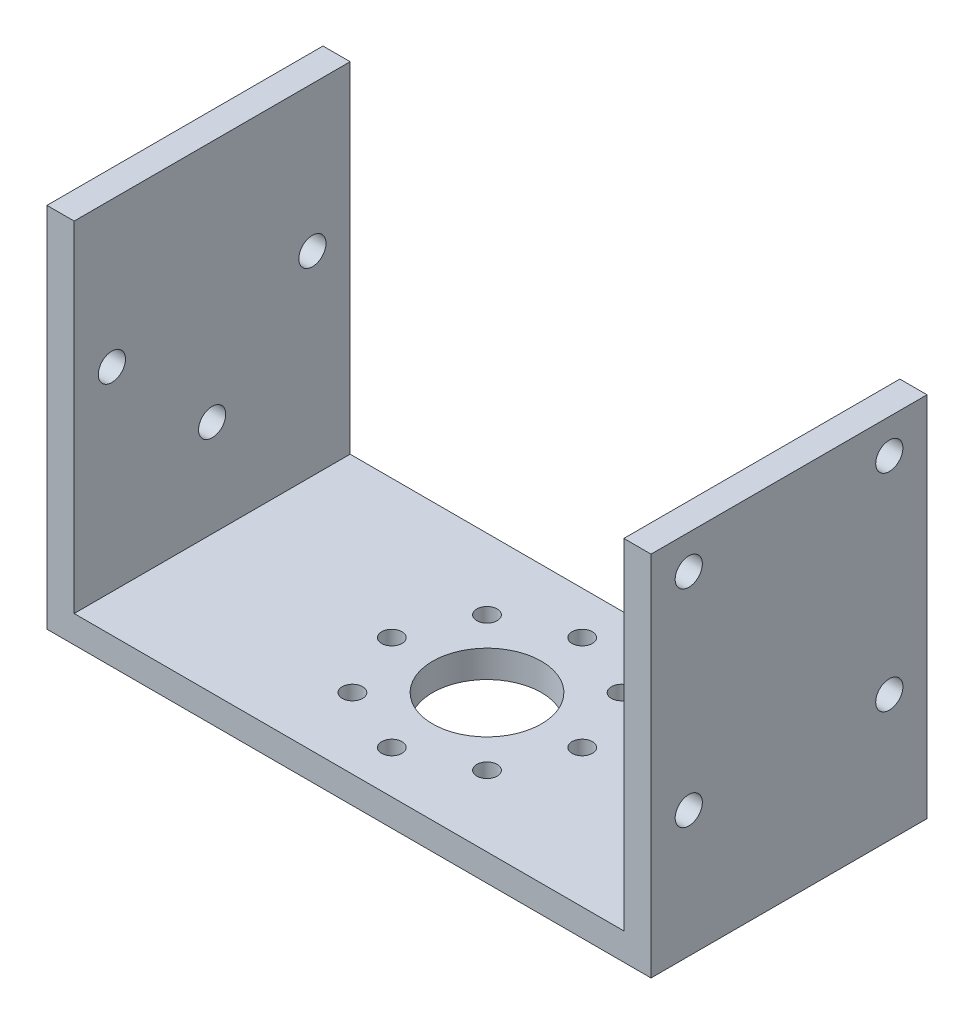
SolidWorks part; units mm, degrees
ref_plane "Front Plane" through (0, 0, 0) normal (0, 0, 1) x (1, 0, 0)
ref_plane "Top Plane" through (0, 0, 0) normal (0, 1, 0) x (1, 0, 0)
ref_plane "Right Plane" through (0, 0, 0) normal (1, 0, 0) x (0, 0, -1)
sketch "Sketch1" plane through (0, 0, 0) normal (0, 1, 0) x (1, 0, 0)
  line L1 (0, 0) -> (44.43, 0)
  line L2 (0, 0) -> (0, 20.3)
  line L3 (0, 20.3) -> (44.43, 20.3)
  line L4 (44.43, 0) -> (44.43, 20.3)
  dimension "D1" = 44.43
  dimension "D2" = 20.3
extrude "YawMount" add sketch "Sketch1" along normal blind 2
sketch "Sketch2" plane through (0, 2, 0) normal (0, 1, 0) x (1, 0, 0)
  line L0 (0, 0) -> (44.43, 0) construction
  line L1 (0, 20.3) -> (2, 20.3)
  line L2 (0, 20.3) -> (0, 0)
  line L3 (0, 0) -> (2, 0)
  line L4 (2, 20.3) -> (2, 0)
  line L6 (44.43, 20.3) -> (42.43, 20.3)
  line L7 (44.43, 20.3) -> (44.43, 0)
  line L8 (44.43, 0) -> (42.43, 0)
  line L9 (42.43, 20.3) -> (42.43, 0)
  dimension "D1" = 2
  dimension "D2" = 2
extrude "BodyConnectors" add sketch "Sketch2" along normal blind 25
sketch "Sketch3" plane through (0, 0, 0) normal (0, -1, 0) x (1, 0, 0)
  line L0 (0, -20.3) -> (0, 0) construction
  line L1 (44.43, -20.3) -> (0, -20.3) construction
  circle A0 centre (22.215, -10.15) radius 4
  point P4 (0, -10.15)
  point P7 (22.215, -20.3)
  dimension "D1" = 8
extrude "Axle-Counterbore" cut sketch "Sketch3" against normal up to surface (2 mm away) up to face at (22.215, 2, -10.15)
sketch "Sketch5" plane through (0, 0, 0) normal (0, -1, 0) x (1, 0, 0)
  line L0 (0, -20.3) -> (0, 0) construction
  line L1 (44.43, -20.3) -> (0, -20.3) construction
  circle A0 centre (15.215, -10.15) radius 0.75
  circle A4 centre (17.2653, -5.2003) radius 0.75
  circle A5 centre (22.215, -3.15) radius 0.75
  circle A6 centre (27.1647, -5.2003) radius 0.75
  circle A7 centre (29.215, -10.15) radius 0.75
  circle A8 centre (27.1647, -15.0997) radius 0.75
  circle A9 centre (22.215, -17.15) radius 0.75
  circle A10 centre (17.2653, -15.0997) radius 0.75
  point P6 (0, -10.15)
  point P24 (22.215, -10.15)
  point P25 (22.215, -20.3)
  dimension "D1" = 1.5
  dimension "D2" = 7
  dimension "D3" = 8
extrude "azel-mountscrews" cut sketch "Sketch5" against normal up to surface (2 mm away) up to face at (22.215, 2, -14.15)
sketch "Sketch6" plane through (2, 0, 0) normal (1, 0, 0) x (0, 0, -1)
  line L0 (0, 27) -> (20.3, 27) construction
  line L3 (0, 2) -> (20.3, 2) construction
  circle A1 centre (10.15, 9.12) radius 1
  circle A2 centre (17.525, 16.33) radius 1
  circle A3 centre (2.775, 16.33) radius 1
  point P5 (10.15, 27)
  dimension "D2" = 2
  dimension "D3" = 14.75
  dimension "D4" = 7.21
  dimension "D5" = 7.375
  dimension "D1" = 7.12
extrude "GearSide-Screws" cut sketch "Sketch6" against normal up to surface (2 mm away) up to face at (0, 13.5, -10.15)
sketch "Sketch7" plane through (42.43, 0, 0) normal (-1, 0, 0) x (0, 0, 1)
  line L0 (-20.3, 2) -> (0, 2) construction
  circle A0 centre (-2.775, 9.3) radius 1
  circle A1 centre (-17.525, 9.3) radius 1
  circle A2 centre (-17.525, 24.5) radius 1
  circle A3 centre (-2.775, 24.5) radius 1
  point P14 (-10.15, 2)
  dimension "D2" = 2
  dimension "D3" = 14.75
  dimension "D1" = 7.3
  dimension "D4" = 7.375
  dimension "D5" = 15.2
extrude "SmoothSide-Screws" cut sketch "Sketch7" against normal up to surface (2 mm away) up to face at (44.43, 13.5, -10.15)
equation "\"srv_w\"= 40.43mm'width of Sain Smart SR319"
equation "\"D1@Sketch1\"=\"srv_w\" + \"mnt_thick\"*2"
equation "\"srv_h\"= 40.61mm'height of Sain Smart SR319"
equation "\"srv_d\"= 20.3mm'depth of Sain Smart SR319"
equation "\"D2@Sketch1\"=\"srv_d\""
equation "\"mnt_thick\"= 2mm'thickness of bracket"
equation "\"D1@YawMount\" = \"mnt_thick\""
equation "\"D2@Sketch2\"=\"mnt_thick\""
equation "\"D1@Sketch2\"=\"mnt_thick\""
equation "\"D5@Sketch6\"=\"D3@Sketch6\"/2"
equation "\"D4@Sketch7\"=\"D3@Sketch7\"/2"
equation "\"clearance\"= 5mm'extra space between bracket and roll rotator servo"
equation "\"D1@Sketch6\"=\"clearance\"+2.12mm"
equation "\"D1@Sketch7\"=\"clearance\"+2.3mm"
equation "\"D1@BodyConnectors\"=20+\"clearance\""
